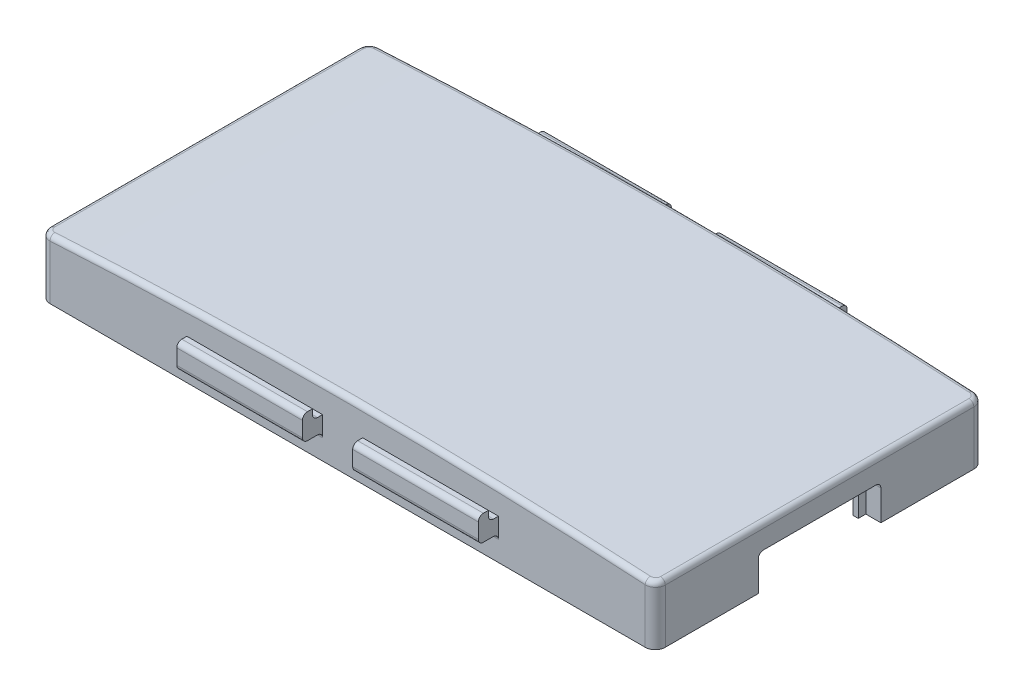
SolidWorks part; units mm, degrees
note: The reader was unsure of these and kept them because the rebuilt part matched: shared geometry of "Sketch2<7>", "Sketch6<3>", "Sketch2<8>", "Sketch13<3>".
ref_plane "Front Plane" through (0, 0, 0) normal (0, 0, 1) x (1, 0, 0)
ref_plane "Top Plane" through (0, 0, 0) normal (0, 1, 0) x (1, 0, 0)
ref_plane "Right Plane" through (0, 0, 0) normal (1, 0, 0) x (0, 0, -1)
sketch "Sketch2" plane through (0, 0, 0) normal (0, 1, 0) x (1, 0, 0)
  line L0 (0, 14.25) -> (0, -14.25) construction
  line L1 (-28.5, -14.25) -> (28.5, -14.25)
  line L2 (-28.5, -14.25) -> (-28.5, 14.25)
  line L3 (-28.5, 14.25) -> (28.5, 14.25)
  line L4 (28.5, -14.25) -> (28.5, 14.25)
  line L5 (-28.5, -14.25) -> (28.5, 14.25) construction
  line L6 (-28.5, 14.25) -> (28.5, -14.25) construction
  line L7 (-28.5, 0) -> (28.5, 0) construction
  line L8 (-30.6, -16.35) -> (-30.6, 16.35)
  line L9 (-28.6, -14.35) -> (28.6, -14.35)
  line L10 (-28.6, -14.35) -> (-28.6, 14.35)
  line L11 (-28.6, 14.35) -> (28.6, 14.35)
  line L12 (28.6, -14.35) -> (28.6, 14.35)
  line L13 (-28.6, -14.35) -> (28.6, 14.35) construction
  line L14 (-28.6, 14.35) -> (28.6, -14.35) construction
  line L15 (-30.6, 16.35) -> (30.6, 16.35)
  line L16 (30.6, -16.35) -> (30.6, 16.35)
  line L17 (-30.6, -16.35) -> (30.6, -16.35)
  line L19 (30.6, -5.35) -> (28.6, -5.35)
  line L20 (30.6, -5.35) -> (30.6, 5.35)
  line L21 (30.6, 5.35) -> (28.6, 5.35)
  line L22 (28.6, -5.35) -> (28.6, 5.35)
  line L31 (-30.6, 16.35) -> (30.6, 16.35) construction
  line L40 (28.6, 5.35) -> (30.6, 5.35) construction
  line L41 (30.6, -5.35) -> (28.6, -5.35) construction
  line L42 (28.5, -14.25) -> (28.5, 14.25) construction
  line L45 (-28.5, -14.25) -> (28.5, -14.25) construction
  line L46 (-28.6, -14.35) -> (-28.6, 14.35) construction
  line L47 (-28.6, 14.35) -> (28.6, 14.35) construction
  line L51 (30.6, 6.1) -> (29.1, 6.1)
  line L52 (30.6, 6.1) -> (30.6, -6.1)
  line L53 (30.6, -6.1) -> (29.1, -6.1)
  line L54 (29.1, 6.1) -> (29.1, -6.1)
  circle A0 centre (-26, 11.75) radius 1.125
  circle A1 centre (-26, -11.75) radius 1.125
  circle A2 centre (26, -11.75) radius 1.125
  circle A3 centre (26, 11.75) radius 1.125
  circle A7 centre (-26, 11.75) radius 1.125 construction
  circle A9 centre (-26, -11.75) radius 1.125 construction
  circle A10 centre (26, -11.75) radius 1.125 construction
  circle A11 centre (26, 11.75) radius 1.125 construction
  point P0 (0, 0)
  point P18 (0, 0)
  dimension "D4" = 1.5
  dimension "D2" = 0.75
  dimension "D3" = 0.75
  dimension "D8" = 2
extrude "Boss-Extrude4" add sketch "Sketch2" along normal blind 0.5
sketch "Sketch5" plane through (0, -3, 0) normal (0, 0, 1) x (1, 0, 0)
  line L4 (-28.6, 3.5) -> (-28.6, 6.5)
  line L7 (28.6, 6.5) -> (28.6, 3.5)
  line L10 (0, 8.25) -> (0, 3) construction
  line L11 (-30.6, 3.5) -> (-30.6, 8.8307)
  line L12 (30.6, 8.8307) -> (30.6, 3.5)
  line L13 (-28.6, 3.5) -> (-30.6, 3.5)
  line L14 (28.6, 3.5) -> (30.6, 3.5)
  line L18 (-30.6, 3) -> (30.6, 3) construction
  arc A0 (27.6, 7.5) -> (28.6, 6.5) centre (27.6, 6.5) cw
  arc A2 (-28.6, 6.5) -> (-27.6, 7.5) centre (-27.6, 6.5) cw
  arc A4 (-27.6, 7.5) -> (27.6, 7.5) centre (0, -499.965) cw
  arc A6 (-30.6, 8.8307) -> (30.6, 8.8307) centre (0, -499.965) cw
  point P7 (0, 8.25)
  dimension "D5" = 27.6
  dimension "D2" = 1
  dimension "D4" = 3
  dimension "D1" = 1.5
  dimension "D3" = 5.25
ref_plane "Plane1" through (30.6, 0, 0) normal (1, 0, 0) x (0, 0, -1)
extrude "Boss-Extrude5" add sketch "Sketch5" along normal up to surface and the other way up to surface up to face at (0, 0.25, 16.35) other way up to face at (0, 0.25, -16.35)
extrude "Boss-Extrude6" add sketch "Sketch2<7>" along normal up to surface (4.5845 mm away) contours A3 | A2 | A0 | A1
sketch "Sketch2<7>" plane through (0, 0, 0) normal (0, 1, 0) x (1, 0, 0) same geometry as "Sketch2"
sketch "Sketch6" plane through (30.6, 0, 0) normal (1, 0, 0) x (0, 0, -1)
  line L0 (-6.1, -1.5) -> (6.1, -1.5) construction
  line L1 (-5.35, 2.75) -> (5.35, 2.75)
  line L2 (-5.35, 2.75) -> (-5.35, -1.5)
  line L3 (-5.35, -1.5) -> (5.35, -1.5)
  line L4 (5.35, 2.75) -> (5.35, -1.5)
  line L5 (5.35, 0) -> (5.35, -1) construction
  line L6 (-5.35, 0.5) -> (-5.35, 0) construction
  line L8 (-6.1, 0) -> (6.1, 0)
  line L9 (-6.1, 0) -> (-6.1, 3.5)
  line L10 (-6.1, 3.5) -> (6.1, 3.5)
  line L11 (6.1, 0) -> (6.1, 3.5)
  line L12 (5.35, 0) -> (16.35, 0) construction
  point P0 (0, 0)
  point P18 (0, 3.5)
  dimension "D1" = 4.25
  dimension "D2" = 0.75
fillet "Fillet3" radius 1 4 edges at (-30.6, 2.9153, 16.35) (-30.6, 2.9153, -16.35) (30.6, 2.9153, -16.35) (30.6, 2.9153, 16.35)
extrude "Cut-Extrude2" cut sketch "Sketch6" against normal up to surface (2 mm away) contours L2 L8 L4 L1 up to face at (28.6, 0.8333, 0)
extrude "Cut-Extrude3" cut sketch "Sketch6<3>" against normal up to surface (1.5 mm away) contours L10 L9 L8 L2 | L8 L11 L10 L4 up to face at (29.1, 0.25, 5.725)
sketch "Sketch6<3>" plane through (30.6, 0, 0) normal (1, 0, 0) x (0, 0, -1) same geometry as "Sketch6"
ref_plane "Plane2" through (0, 0.5, 0) normal (0, 1, 0) x (1, 0, 0)
ref_plane "Plane4" through (0, 2, 0) normal (0, 1, 0) x (1, 0, 0)
extrude "Boss-Extrude7" add sketch "Sketch2<8>" along normal up to body from surface separate body
sketch "Sketch2<8>" plane through (0, 0, 0) normal (0, 1, 0) x (1, 0, 0) same geometry as "Sketch2"
fillet "Fillet5" radius 0.5 4 edges at (28.85, 2.75, -5.35) (28.85, 2.75, 5.35) (29.85, 3.5, 6.1) (29.85, 3.5, -6.1)
sketch "Sketch11" plane through (0, 0, 0) normal (0, 0, 1) x (1, 0, 0)
  line L0 (-28.6, 0) -> (28.6, 0) construction
  line L1 (14.6, 0) -> (23.6, 0)
  line L2 (14.6, 0) -> (14.6, 1.0042)
  line L4 (23.6, 0) -> (23.6, 0.361)
  line L5 (22.6915, 1.3568) -> (15.6915, 2)
  line L9 (28.6, 3.5) -> (28.6, 0.5) construction
  arc A0 (15.6915, 2) -> (14.6, 1.0042) centre (15.6, 1.0042) ccw
  arc A1 (22.6915, 1.3568) -> (23.6, 0.361) centre (22.6, 0.361) cw
  dimension "D1" = 1
  dimension "D2" = 9
  dimension "D3" = 5
  dimension "D4" = 2
  dimension "D5" = 5.25
extrude "Cut-Extrude4" [suppressed] cut sketch "Sketch11" against normal through all
sketch "Sketch12" plane through (0, 0, 0) normal (0, 1, 0) x (1, 0, 0)
  line L0 (-29.6, -15.35) -> (-29.6, 15.35)
  line L1 (-28.6, -14.35) -> (28.6, -14.35)
  line L2 (-28.6, -14.35) -> (-28.6, 14.35)
  line L3 (-28.6, 14.35) -> (28.6, 14.35)
  line L4 (28.6, -14.35) -> (28.6, 14.35)
  line L5 (-29.6, 15.35) -> (29.6, 15.35)
  line L6 (29.6, -15.35) -> (29.6, 15.35)
  line L7 (-29.6, -15.35) -> (29.6, -15.35)
  line L8 (29.1, -6.1) -> (30.6, -6.1) construction
  line L9 (29.6, -6.1) -> (28.6, -6.1)
  line L10 (29.6, -6.1) -> (29.6, 6.1)
  line L11 (29.6, 6.1) -> (28.6, 6.1)
  line L12 (28.6, -6.1) -> (28.6, 6.1)
  line L13 (29.1, 6.1) -> (30.6, 6.1) construction
  line L14 (28.6, -7.6) -> (29.6, -7.6)
  line L15 (28.6, 7.6) -> (29.6, 7.6)
  dimension "D2" = 1.5
  dimension "D3" = 1.5
  dimension "D1" = 1
extrude "Cut-Extrude5" cut sketch "Sketch12" along normal blind 2.5 contours L11 L6 L5 L0 L7 L9 L4 L1 L2 L3
sketch "Sketch13" plane through (0, 0, 0) normal (1, 0, 0) x (0, 0, -1)
  line L0 (-16.35, 2.5) -> (-18.35, 2.5)
  line L1 (-16.35, 0) -> (-16.35, 5.8898) construction
  line L2 (-18.35, 2.5) -> (-18.35, 5)
  line L3 (-18.35, 5) -> (-17.35, 5)
  line L4 (-17.35, 5) -> (-17.35, 4)
  line L5 (-17.35, 4) -> (-16.35, 4)
  line L6 (-16.35, 0) -> (-15.35, 0) construction
  line L7 (-16.35, 4) -> (-16.35, 2.5)
  dimension "D1" = 2.5
  dimension "D2" = 1.5
  dimension "D3" = 2
  dimension "D4" = 1
  dimension "D5" = 1
extrude "rail" add sketch "Sketch13" along normal mid plane 30 contours L7 L0 L2 L3 L4 L5
extrude "Cut-Extrude6" cut sketch "Sketch13<3>" against normal mid plane 5
sketch "Sketch13<3>" plane through (0, 0, 0) normal (1, 0, 0) x (0, 0, -1) same geometry as "Sketch13"
fillet "Fillet7" radius 0.5 6 edges at (-8.75, 4, 17.35) (8.75, 4, 17.35) (-8.75, 5, 18.35) (8.75, 5, 18.35) (-8.75, 2.5, 18.35) (8.75, 2.5, 18.35)
mirror "Mirror1" about plane through (0, 0, 0) normal (0, 0, 1) of "Fillet7", "Cut-Extrude6", "rail"
fillet "Fillet8" radius 0.5 4 edges at (-8.75, 2.5, 16.35) (8.75, 2.5, 16.35) (-8.75, 2.5, -16.35) (8.75, 2.5, -16.35)
sketch "Sketch14" plane through (0, 0, 0) normal (0, 1, 0) x (1, 0, 0)
  line L0 (-16.5, -16.35) -> (-16.5, -17.85)
  line L1 (-29.6, -16.35) -> (29.6, -16.35) construction
  line L2 (-16.5, -17.85) -> (-18, -17.85)
  line L3 (-18, -17.85) -> (-18, -19.35)
  line L4 (-18, -19.35) -> (-12, -19.35)
  line L5 (-12, -19.35) -> (-12, -17.85)
  line L6 (-12, -17.85) -> (-13.5, -17.85)
  line L7 (-13.5, -17.85) -> (-13.5, -16.35)
  line L8 (-16.5, -16.35) -> (-13.5, -16.35)
  line L9 (-13.5, -16.35) -> (-13.5, -15.85)
  line L10 (-13.5, -15.85) -> (-12, -15.85)
  line L11 (-12, -15.85) -> (-12, -14.35)
  line L12 (-12, -14.35) -> (-18, -14.35)
  line L13 (-18, -14.35) -> (-18, -15.85)
  line L14 (-18, -15.85) -> (-16.5, -15.85)
  line L15 (-16.5, -15.85) -> (-16.5, -16.35)
  line L16 (-13.5, -15.85) -> (-13.5, -16.35)
  point P4 (-15, -14.35)
  point P11 (-15, -16.35)
  dimension "D1" = 1.5
  dimension "D2" = 1.5
  dimension "D3" = 1.5
  dimension "D4" = 1.5
  dimension "D5" = 3
  dimension "D6" = 15
  dimension "D7" = 1.5
  dimension "D8" = 1.5
  dimension "D9" = 0.5
extrude "slot" [suppressed] cut sketch "Sketch14" along normal through all contours L14 L15 L8 L9 L10 L11 L12 L13
mirror "Mirror4" [suppressed] about plane through (0, 0, 0) normal (0, 0, 1)
mirror "Mirror5" [suppressed] about plane through (0, 0, 0) normal (1, 0, 0)
fillet "Fillet9" radius 0.5 8 edges at (-30.2255, 5.853, -16.1302) (0, 6.75, -16.35) (30.3815, 5.8437, -15.9739) (30.6, 5.8307, 0) (30.2255, 5.853, 16.1302) (0, 6.75, 16.35) (-30.3815, 5.8437, 15.9739) (-30.6, 5.8307, 0)
